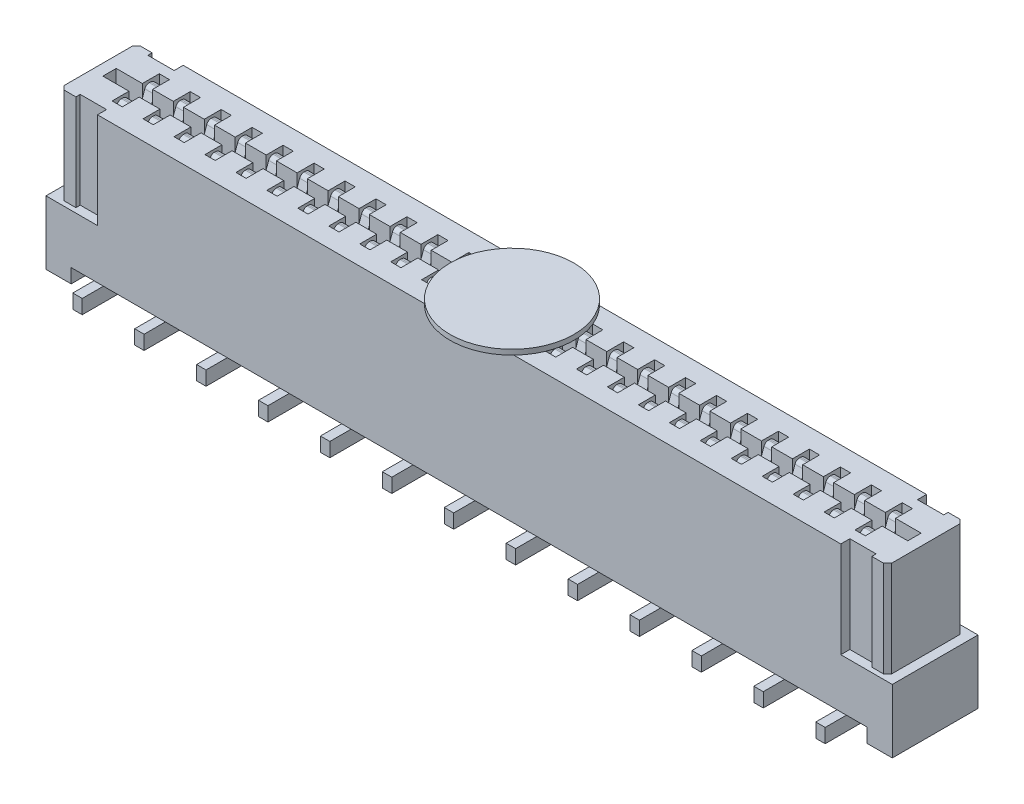
SolidWorks part; units mm, degrees
ref_plane "Front" through (0, 0, 0) normal (0, 0, 1) x (1, 0, 0)
ref_plane "Top" through (0, 0, 0) normal (0, 1, 0) x (1, 0, 0)
ref_plane "Side" through (0, 0, 0) normal (1, 0, 0) x (0, 0, -1)
sketch "Sketch1" plane through (0, 0, 0) normal (0, 0, 1) x (1, 0, 0)
  line L0 (-13.6684, 2.6416) -> (-13.6684, -2.5146)
  line L1 (-13.6684, -2.5146) -> (13.6684, -2.5146)
  line L2 (13.6684, -2.5146) -> (13.6684, 2.6416)
  line L3 (13.6684, 2.6416) -> (-13.6684, 2.6416)
  line L4 (0, 2.6416) -> (0, -2.5146) construction
  line L5 (0, -24.1149) -> (0, 24.1149) construction
  dimension "D1" = 27.3368
  dimension "D2" = 5.1562
  dimension "D4" = 2.6416
extrude "Base" add sketch "Sketch1" along normal mid plane 2.7686
sketch "Sketch2" plane through (13.6684, 0, 0) normal (1, 0, 0) x (0, 0, -1)
  line L0 (-1.3843, 2.6416) -> (1.3843, 2.6416)
  line L1 (1.3843, 2.6416) -> (1.3843, -0.4572)
  line L2 (1.3843, -0.4572) -> (-1.3843, -0.4572)
  line L3 (-1.3843, -2.5146) -> (-1.3843, 2.6416) construction
  line L4 (-1.3843, -0.4572) -> (-1.3843, 2.6416)
  dimension "D1" = 3.0988
extrude "Side Cut" cut sketch "Sketch2" against normal blind 0.3048
sketch "Sketch3" plane through (0, 0, 1.3843) normal (0, 0, 1) x (1, 0, 0)
  line L0 (13.3636, 2.6416) -> (13.3636, -0.4572)
  line L1 (13.3636, -0.4572) -> (12.8556, -0.4572)
  line L2 (12.8556, -0.4572) -> (12.8556, 2.6416)
  line L3 (12.8556, 2.6416) -> (13.3636, 2.6416)
  dimension "D1" = 0.508
extrude "Weld Tab Slot" cut sketch "Sketch3" against normal blind 0.1524
sketch "Sketch4" plane through (0, 0, 1.3843) normal (0, 0, 1) x (1, 0, 0)
  line L0 (12.8556, 2.6416) -> (12.8556, -0.4572)
  line L1 (12.8556, -0.4572) -> (12.0047, -0.4572)
  line L2 (12.0047, -0.4572) -> (12.0047, 2.6416)
  line L3 (12.8556, 2.6416) -> (-13.6684, 2.6416) construction
  line L4 (12.0047, 2.6416) -> (12.8556, 2.6416)
  dimension "D1" = 0.8509
extrude "WT Retention Slot" cut sketch "Sketch4" against normal blind 0.2921
sketch "Sketch5" plane through (0, -2.5146, 0) normal (0, -1, 0) x (1, 0, 0)
  line L0 (-12.8556, 1.3843) -> (-12.8556, -1.3843)
  line L1 (12.8556, 1.0922) -> (12.8556, 1.2319) construction
  line L3 (-12.8556, -1.3843) -> (12.8556, -1.3843)
  line L4 (12.8556, -1.3843) -> (12.8556, 1.3843)
  line L5 (12.8556, 1.3843) -> (-12.8556, 1.3843)
  line L7 (0, -1.3843) -> (0, 1.3843) construction
  line L9 (0, -24.1149) -> (0, 24.1149) construction
  line L10 (-13.6684, 1.3843) -> (13.6684, 1.3843) construction
  line L11 (-13.6684, -1.3843) -> (13.6684, -1.3843) construction
extrude "Standoff" cut sketch "Sketch5" against normal blind 0.4572
mirror "Mirror8" about plane through (0, 0, 0) normal (0, 0, 1) of "Weld Tab Slot", "WT Retention Slot"
mirror "Mirror10" about plane through (0, 0, 0) normal (1, 0, 0) of "WT Retention Slot", "Side Cut", "Weld Tab Slot", "Mirror8"
sketch "Sketch7" plane through (0, -2.0574, 0) normal (0, -1, 0) x (1, 0, 0)
  line L0 (12.174, 0.9144) -> (12.174, -0.9144)
  line L1 (12.174, -0.9144) -> (11.8438, -0.9144)
  line L2 (11.8438, -0.9144) -> (11.8438, 0.9144)
  line L3 (11.8438, 0.9144) -> (12.174, 0.9144)
  line L6 (12.0089, 0.9144) -> (12.0089, -0.9144) construction
  line L7 (11.8438, 0) -> (12.174, 0) construction
  line L8 (17.5453, 0) -> (-17.5453, 0) construction
  line L9 (13.6684, 1.3843) -> (13.6684, -1.3843) construction
  dimension "D1" = 0.3302
  dimension "D2" = 1.8288
  dimension "D3" = 1.6595
extrude "Slot Cut" cut sketch "Sketch7" against normal blind 1.397
sketch "Sketch8" plane through (0, -0.6604, 0) normal (0, -1, 0) x (1, 0, 0)
  line L0 (12.174, 0.762) -> (12.174, -0.762)
  line L1 (11.8438, -0.9144) -> (11.8438, 0.9144) construction
  line L2 (12.174, -0.762) -> (11.8438, -0.762)
  line L3 (12.174, 0.9144) -> (12.174, -0.9144) construction
  line L4 (12.174, 0.762) -> (11.8438, 0.762)
  line L5 (11.8438, -0.762) -> (11.8438, 0.762)
  line L7 (11.8438, 0) -> (12.174, 0) construction
  line L10 (11.8438, -0.9144) -> (11.8438, 0.9144) construction
  line L11 (12.174, 0.9144) -> (12.174, -0.9144) construction
  line L12 (11.8438, 0) -> (12.174, 0) construction
  dimension "D2" = 1.524
extrude "Cut-Extrude7" cut sketch "Sketch8" against normal up to surface (3.302 mm away) up to face at (-12.8556, 1.0922, -1.1621)
sketch "Sketch10" plane through (0, 2.6416, 0) normal (0, 1, 0) x (-1, 0, 0)
  line L0 (13, -0.2159) -> (-13, -0.2159)
  line L1 (-13, -0.2159) -> (-13, 0.2159)
  line L2 (-13, 0.2159) -> (13, 0.2159)
  line L3 (13, 0.2159) -> (13, -0.2159)
  line L4 (13, 0) -> (-13, 0) construction
  line L5 (17.5453, 0) -> (-17.5453, 0) construction
  line L6 (0, -0.2159) -> (0, 0.2159) construction
  line L7 (0, 24.1149) -> (0, -24.1149) construction
  line L9 (-13.6684, -1.3843) -> (-13.6684, 1.3843) construction
  dimension "D1" = 0.4318
  dimension "D2" = 0.6684
extrude "Card slot" cut sketch "Sketch10" against normal blind 3.4544
pattern_linear "Position Pattern" count 25 spacing 1 along (-1, 0, 0) of "Slot Cut", "Cut-Extrude7"
chamfer "Chamfer1" distance 0.127 angle 45 4 edges at (-13.3636, 1.0922, -1.2319) (13.3636, 1.0922, -1.2319) (13.3636, 1.0922, 1.2319) (-13.3636, 1.0922, 1.2319)
ref_plane "-01 Pin Plane" through (11.0089, 0, 0) normal (1, 0, 0) x (0, 0, -1)
sketch "Sketch11" plane through (11.0089, 0, 0) normal (1, 0, 0) x (0, 0, -1)
  line L0 (-1.1049, 2.6416) -> (1.1049, 2.6416) construction
  line L1 (0, -0.8128) -> (0, 0.397) construction
  line L2 (0.2159, -0.8128) -> (-0.2159, -0.8128) construction
  line L3 (0, -0.7366) -> (0, 0.6904) construction
  line B0 (0.6223, 2.413) -> (0.6223, -0.2527)
  line B1 (0.4699, 2.5654) -> (0.4276, 2.5654)
  line B2 (0.284, 2.464) -> (0.0855, 1.9056)
  line B3 (0.2578, 1.1679) -> (0.0857, 1.6499)
  line B4 (0.2667, 1.1166) -> (0.2667, -0.4699)
  line B5 (-0.284, 2.464) -> (-0.0855, 1.9056)
  line B6 (-0.4699, 2.5654) -> (-0.4276, 2.5654)
  line B7 (-0.6223, 2.413) -> (-0.6223, -0.2527)
  line B8 (-0.2578, 1.1679) -> (-0.0857, 1.6499)
  line B9 (-0.2667, 1.1166) -> (-0.2667, -0.4699)
  line B10 (-0.9017, -0.7366) -> (-0.6223, -0.2527)
  line B11 (0.6223, -0.2527) -> (0.9017, -0.7366)
  line B12 (0.9017, -2.0828) -> (0.9017, -0.7366)
  line B13 (-0.9017, -0.7366) -> (-0.9017, -2.2098)
  line B14 (0.9017, -2.0828) -> (2.0447, -2.0828)
  line B15 (2.0447, -2.0828) -> (2.0447, -2.54)
  line B16 (2.0447, -2.54) -> (0.5334, -2.54)
  line B17 (0.4064, -2.2098) -> (0.4064, -2.413)
  line B18 (0.4064, -2.2098) -> (-0.9017, -2.2098)
  arc B19 (0.4699, 2.5654) -> (0.6223, 2.413) centre (0.4699, 2.413) cw
  arc B20 (0.284, 2.464) -> (0.4276, 2.5654) centre (0.4276, 2.413) cw
  arc B21 (0.0857, 1.6499) -> (0.0855, 1.9056) centre (0.4445, 1.778) cw
  arc B22 (0.2578, 1.1679) -> (0.2667, 1.1166) centre (0.1143, 1.1166) cw
  arc B23 (-0.4276, 2.5654) -> (-0.284, 2.464) centre (-0.4276, 2.413) cw
  arc B24 (-0.6223, 2.413) -> (-0.4699, 2.5654) centre (-0.4699, 2.413) cw
  arc B25 (-0.0855, 1.9056) -> (-0.0857, 1.6499) centre (-0.4445, 1.778) cw
  arc B26 (-0.2667, 1.1166) -> (-0.2578, 1.1679) centre (-0.1143, 1.1166) cw
  arc B27 (0, -0.7366) -> (-0.2667, -0.4699) centre (0, -0.4699) cw
  arc B28 (0.2667, -0.4699) -> (0, -0.7366) centre (0, -0.4699) cw
  arc B29 (0.5334, -2.54) -> (0.4064, -2.413) centre (0.5334, -2.413) cw
  dimension "D1" = 5.1816
sketch_block_instance "FC1-3"
sketch_block "FC1"
extrude "-01 Lead Style Pin (R)" add sketch "Sketch11" along normal mid plane 0.3048
pattern_linear "-01 Pin (R) Pattern" count 12 spacing 2 along (-1, 0, 0) of "-01 Lead Style Pin (R)"
ref_plane "-01 Pin Plane 2" through (12.0089, 0, 0) normal (1, 0, 0) x (0, 0, -1)
sketch "Sketch12" plane through (12.0089, 0, 0) normal (1, 0, 0) x (0, 0, -1)
  line L0 (0, -0.7366) -> (0, 0.7071) construction
  line L1 (0.5334, -2.54) -> (2.0447, -2.54) construction
  line L2 (0, 0) -> (0, -1.2651) construction
  line B0 (-0.6223, 2.413) -> (-0.6223, -0.2527)
  line B1 (-0.4699, 2.5654) -> (-0.4276, 2.5654)
  line B2 (-0.284, 2.464) -> (-0.0855, 1.9056)
  line B3 (-0.2578, 1.1679) -> (-0.0857, 1.6499)
  line B4 (-0.2667, 1.1166) -> (-0.2667, -0.4699)
  line B5 (0.284, 2.464) -> (0.0855, 1.9056)
  line B6 (0.4699, 2.5654) -> (0.4276, 2.5654)
  line B7 (0.6223, 2.413) -> (0.6223, -0.2527)
  line B8 (0.2578, 1.1679) -> (0.0857, 1.6499)
  line B9 (0.2667, 1.1166) -> (0.2667, -0.4699)
  line B10 (0.9017, -0.7366) -> (0.6223, -0.2527)
  line B11 (-0.6223, -0.2527) -> (-0.9017, -0.7366)
  line B12 (-0.9017, -2.0828) -> (-0.9017, -0.7366)
  line B13 (0.9017, -0.7366) -> (0.9017, -2.2098)
  line B14 (-0.9017, -2.0828) -> (-2.0447, -2.0828)
  line B15 (-2.0447, -2.0828) -> (-2.0447, -2.54)
  line B16 (-2.0447, -2.54) -> (-0.5334, -2.54)
  line B17 (-0.4064, -2.2098) -> (-0.4064, -2.413)
  line B18 (-0.4064, -2.2098) -> (0.9017, -2.2098)
  arc B19 (-0.4699, 2.5654) -> (-0.6223, 2.413) centre (-0.4699, 2.413) ccw
  arc B20 (-0.284, 2.464) -> (-0.4276, 2.5654) centre (-0.4276, 2.413) ccw
  arc B21 (-0.0857, 1.6499) -> (-0.0855, 1.9056) centre (-0.4445, 1.778) ccw
  arc B22 (-0.2578, 1.1679) -> (-0.2667, 1.1166) centre (-0.1143, 1.1166) ccw
  arc B23 (0.4276, 2.5654) -> (0.284, 2.464) centre (0.4276, 2.413) ccw
  arc B24 (0.6223, 2.413) -> (0.4699, 2.5654) centre (0.4699, 2.413) ccw
  arc B25 (0.0855, 1.9056) -> (0.0857, 1.6499) centre (0.4445, 1.778) ccw
  arc B26 (0.2667, 1.1166) -> (0.2578, 1.1679) centre (0.1143, 1.1166) ccw
  arc B27 (0, -0.7366) -> (0.2667, -0.4699) centre (0, -0.4699) ccw
  arc B28 (-0.2667, -0.4699) -> (0, -0.7366) centre (0, -0.4699) ccw
  arc B29 (-0.5334, -2.54) -> (-0.4064, -2.413) centre (-0.5334, -2.413) ccw
sketch_block_instance "FC1-5"
extrude "-01 Lead Style Pin (L)" add sketch "Sketch12" along normal mid plane 0.3048
pattern_linear "-01 Pin (L) Pattern" count 13 spacing 2 along (-1, 0, 0) of "-01 Lead Style Pin (L)"
ref_plane "-02 Pin Plane" [suppressed] through (12.0089, 0, 0) normal (1, 0, 0) x (0, 0, -1)
sketch "Sketch13" plane through (0, -0.4572, 0) normal (0, 1, 0) x (1, 0, 0)
  line L0 (0, 0) -> (4.4134, 0) construction
  line L1 (13.3636, -1.1049) -> (13.3636, 1.1049) construction
  line L2 (-13.3636, 1.1049) -> (-13.3636, -1.1049) construction
  line B0 (12.0428, -1.397) -> (13.2112, -1.397)
  arc B1 (13.516, 1.0922) -> (13.2112, 1.397) centre (13.2112, 1.0922) ccw
  line B2 (13.3636, 1.0922) -> (13.3636, -1.0922)
  line B3 (13.2112, -1.2446) -> (12.0428, -1.2446)
  line B4 (13.2112, 1.397) -> (12.0428, 1.397)
  arc B5 (13.3636, 1.0922) -> (13.2112, 1.2446) centre (13.2112, 1.0922) ccw
  arc B6 (13.2112, -1.2446) -> (13.3636, -1.0922) centre (13.2112, -1.0922) ccw
  line B7 (13.516, -1.0922) -> (13.516, 1.0922)
  line B8 (12.0428, 1.397) -> (12.0428, 1.2446)
  line B9 (12.0428, 1.2446) -> (13.2112, 1.2446)
  line B10 (12.0428, -1.2446) -> (12.0428, -1.397)
  arc B11 (13.2112, -1.397) -> (13.516, -1.0922) centre (13.2112, -1.0922) ccw
  line B12 (-12.0428, 1.397) -> (-13.2112, 1.397)
  arc B13 (-13.516, -1.0922) -> (-13.2112, -1.397) centre (-13.2112, -1.0922) ccw
  line B14 (-13.3636, -1.0922) -> (-13.3636, 1.0922)
  line B15 (-13.2112, 1.2446) -> (-12.0428, 1.2446)
  line B16 (-13.2112, -1.397) -> (-12.0428, -1.397)
  arc B17 (-13.3636, -1.0922) -> (-13.2112, -1.2446) centre (-13.2112, -1.0922) ccw
  arc B18 (-13.2112, 1.2446) -> (-13.3636, 1.0922) centre (-13.2112, 1.0922) ccw
  line B19 (-13.516, 1.0922) -> (-13.516, -1.0922)
  line B20 (-12.0428, -1.397) -> (-12.0428, -1.2446)
  line B21 (-12.0428, -1.2446) -> (-13.2112, -1.2446)
  line B22 (-12.0428, 1.2446) -> (-12.0428, 1.397)
  arc B23 (-13.2112, 1.397) -> (-13.516, 1.0922) centre (-13.2112, 1.0922) ccw
sketch_block_instance "FC1-WT-1"
sketch_block "FC1-WT"
sketch_block_instance "FC1-WT-3" parameters "D1"=4.4134
ref_plane "-LC Plane" [suppressed] through (3.262, 0, 0) normal (1, 0, 0) x (0, 0, -1)
sketch "Sketch17" plane through (0, 2.6416, 0) normal (0, 1, 0) x (1, 0, 0)
  circle A0 centre (0, 0) radius 2.0002
  dimension "D1" = 4.0005
extrude "-KAPTON" add sketch "Sketch17" along normal blind 0.1651
equation "\"D1@Sketch1\" = \"D1@Position Pattern\" * .03937 + .092"
equation "\"D2@Sketch10\" = \"D1@Position Pattern\" * .03937 + .03937"
